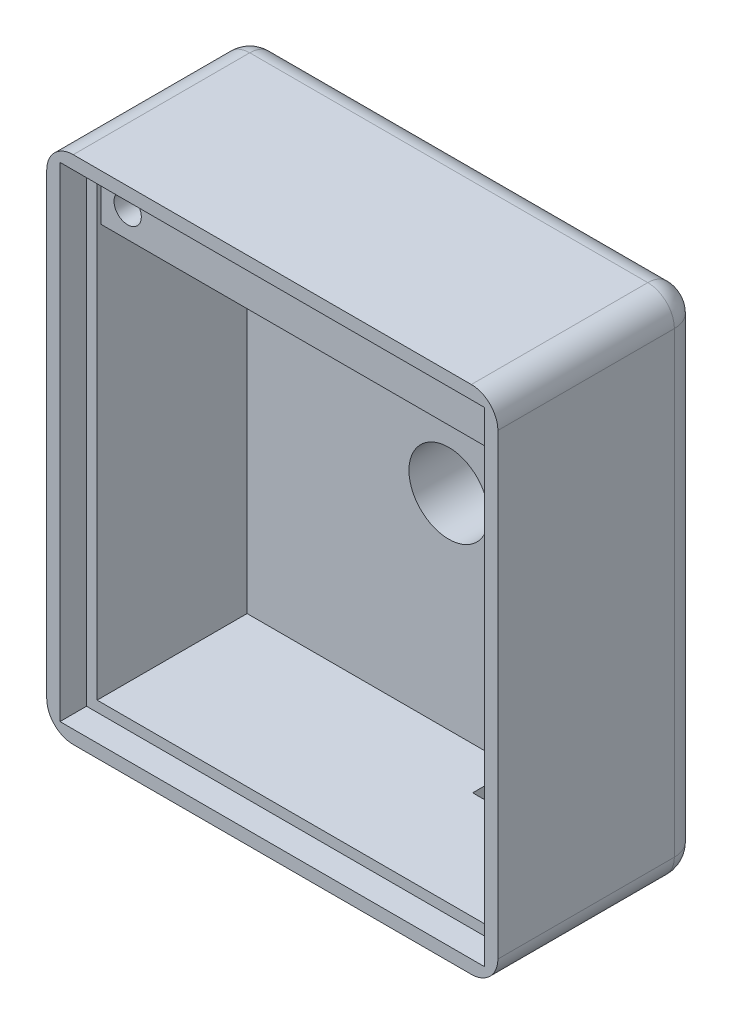
SolidWorks part; units mm, degrees
ref_plane "Front Plane" through (0, 0, 0) normal (0, 0, 1) x (1, 0, 0)
ref_plane "Top Plane" through (0, 0, 0) normal (0, 1, 0) x (1, 0, 0)
ref_plane "Right Plane" through (0, 0, 0) normal (1, 0, 0) x (0, 0, -1)
sketch "Sketch1" plane through (0, 0, 0) normal (0, 0, 1) x (1, 0, 0)
  line L1 (-8.25, 36.25) -> (25.75, 36.25)
  line L2 (-8.25, 36.25) -> (-8.25, -2.25)
  line L3 (-8.25, -2.25) -> (25.75, -2.25)
  line L4 (25.75, 36.25) -> (25.75, -2.25)
  dimension "D1" = 34
  dimension "D2" = 38.5
extrude "Extrude1" add sketch "Sketch1" against normal blind 10 and the other way blind 5.3
sketch "Sketch2" plane through (0, 0, -10) normal (0, 0, -1) x (-1, 0, 0)
  line L1 (-8.75, 36.25) -> (-8.75, -2.25) construction
  line L2 (-25.75, 36.25) -> (8.25, 36.25) construction
  line L3 (8.25, -2.25) -> (-25.75, -2.25) construction
  line L4 (-25.75, 17) -> (8.25, 17) construction
  line L7 (-25.75, -2.25) -> (-25.75, 36.25) construction
  line L8 (8.25, 36.25) -> (8.25, -2.25) construction
  circle A0 centre (-8.75, 17) radius 8
  dimension "D1" = 16
sketch "Sketch5" plane through (0, 0, 5.3) normal (0, 0, 1) x (1, 0, 0)
  line L0 (25.75, -2.25) -> (25.75, 36.25) construction
  line L1 (24.75, -1.25) -> (-7.25, -1.25)
  line L2 (24.75, -1.25) -> (24.75, 35.25)
  line L3 (24.75, 35.25) -> (-7.25, 35.25)
  line L4 (-7.25, -1.25) -> (-7.25, 35.25)
  line L5 (-8.25, -2.25) -> (25.75, -2.25) construction
  line L6 (-8.25, 36.25) -> (-8.25, -2.25) construction
  line L7 (25.75, 36.25) -> (-8.25, 36.25) construction
  dimension "D1" = 1
  dimension "D2" = 1
  dimension "D3" = 1
  dimension "D4" = 1
extrude "Cut-Extrude2" cut sketch "Sketch5" against normal blind 2
sketch "Sketch6" plane through (0, 0, 3.3) normal (0, 0, 1) x (1, 0, 0)
  line L0 (25.75, -2.25) -> (25.75, 36.25) construction
  line L1 (23.95, -0.45) -> (-6.45, -0.45)
  line L2 (23.95, -0.45) -> (23.95, 34.45)
  line L3 (23.95, 34.45) -> (-6.45, 34.45)
  line L4 (-6.45, -0.45) -> (-6.45, 34.45)
  line L5 (-8.25, -2.25) -> (25.75, -2.25) construction
  line L6 (-8.25, 36.25) -> (-8.25, -2.25) construction
  line L7 (25.75, 36.25) -> (-8.25, 36.25) construction
  dimension "D1" = 1.8
  dimension "D2" = 1.8
  dimension "D3" = 1.8
  dimension "D4" = 1.8
extrude "Cut-Extrude3" cut sketch "Sketch6" against normal blind 11.3 and the other way blind 0.2
fillet "Fillet1" radius 2 8 edges at (8.75, 36.25, -10) (-8.25, 17, -10) (25.75, 17, -10) (8.75, -2.25, -10) (25.75, -2.25, -2.35) (25.75, 36.25, -2.35) (-8.25, -2.25, -2.35) (-8.25, 36.25, -2.35)
sketch "Sketch11" plane through (0, 0, -8) normal (0, 0, 1) x (1, 0, 0)
  line L0 (-6.45, 34.45) -> (23.95, 34.45) construction
  line L1 (23.95, 34.45) -> (23.95, 30.45)
  line L2 (23.95, -0.45) -> (23.95, 34.45) construction
  line L3 (-6.45, 34.45) -> (-0.45, 29.95) construction
  line L4 (23.95, 30.45) -> (-6.45, 30.45)
  line L5 (23.95, 34.45) -> (-6.45, 34.45)
  line L6 (-6.45, 30.45) -> (-6.45, 34.45)
  dimension "D1" = 30.4
  dimension "D2" = 4
extrude "Extrude4" add sketch "Sketch11" along normal blind 11
hole_wizard "#1 Clearance Hole1" positions "Sketch13" profile "Sketch12" hole size "#1" standard "Ansi Inch"
sketch "Sketch13" plane through (0, 0, 3.3) normal (0, 0, 1) x (1, 0, 0)
  line L2 (23.75, 36.25) -> (-6.25, 36.25) construction
  line L3 (-8.25, 34.25) -> (-8.25, -0.25) construction
  point P0 (-4.45, 32.45)
  dimension "D1" = 3.8
  dimension "D2" = 3.8
sketch "Sketch12" plane through (-4.45, 32.45, 3.3) normal (1, 0, 0) x (0, -1, 0)
  line L0 (0, 0) -> (0, 8.6181)
  line L1 (0, 8.6181) -> (1.0287, 8)
  line L2 (1.0287, 8) -> (1.0287, 0)
  line L5 (1.0287, 0) -> (0, 0)
  line L10 (0, 8.6181) -> (-1.0287, 8) construction
  line L11 (0, -6.35) -> (0, 107.95) construction
  dimension "Hole Dia." = 2.0574
  dimension "Hole Depth" = 8
  dimension "Drill Angle" = 118
sketch "Sketch17" plane through (0, 0, -10) normal (0, 0, -1) x (-1, 0, 0)
  line L0 (6.45, 30.45) -> (6.45, -0.45) construction
  line L1 (6.45, 15) -> (-23.95, 15) construction
  line L2 (-23.95, -0.45) -> (-23.95, 30.45) construction
  line L3 (-8.75, 30.45) -> (-8.75, -0.45) construction
  line L4 (6.45, 30.45) -> (-23.95, 30.45) construction
  line L7 (-23.95, -0.45) -> (6.45, -0.45) construction
  circle A0 centre (-8.75, 15) radius 3
  dimension "D1" = 6
extrude "Cut-Extrude6" cut sketch "Sketch17" against normal blind 10
sketch "Sketch18" plane through (0, 0, -8) normal (0, 0, 1) x (1, 0, 0)
  line L1 (-6.45, 30.45) -> (-3.45, 30.45)
  line L2 (-6.45, 30.45) -> (-6.45, 27.45)
  line L3 (-6.45, 27.45) -> (-3.45, 27.45)
  line L4 (-3.45, 30.45) -> (-3.45, 27.45)
  dimension "D1" = 3
  dimension "D2" = 3
extrude "Extrude5" add sketch "Sketch18" along normal blind 2.3
sketch "Sketch19" plane through (0, -2.25, 0) normal (0, -1, 0) x (1, 0, 0)
  line L0 (25.75, 5.3) -> (25.75, -8) construction
  line L4 (13.75, -4.8) -> (22.05, -4.8)
  line L5 (13.75, -4.8) -> (13.75, -8)
  line L6 (13.75, -8) -> (22.05, -8)
  line L7 (22.05, -4.8) -> (22.05, -8)
  line L8 (23.75, -10) -> (-6.25, -10) construction
  dimension "D1" = 3.7
  dimension "D2" = 8.3
  dimension "D3" = 3.2
  dimension "D4" = 2
extrude "Cut-Extrude7" cut sketch "Sketch19" against normal blind 3
sketch "Sketch20" plane through (0, 0, -10) normal (0, 0, -1) x (-1, 0, 0)
  circle A1 centre (-8.75, 15) radius 3 construction
  circle A3 centre (-8.75, 15) radius 8.5
  dimension "D1" = 17
extrude "Extrude6" add sketch "Sketch20" along normal blind 6
sketch "Sketch21" plane through (0, 0, -16) normal (0, 0, -1) x (-1, 0, 0)
  circle A3 centre (-8.75, 15) radius 6.6
  dimension "D1" = 13.2
extrude "Cut-Extrude8" cut sketch "Sketch21" against normal blind 6
sketch "Sketch22" plane through (0, 0, -10) normal (0, 0, -1) x (-1, 0, 0)
  circle A3 centre (-8.75, 15) radius 4.45
  dimension "D1" = 8.9
extrude "Extrude7" add sketch "Sketch22" along normal blind 6
sketch "Sketch23" plane through (0, 0, -16) normal (0, 0, -1) x (-1, 0, 0)
  circle A3 centre (-8.75, 15) radius 3
  dimension "D1" = 6
extrude "Cut-Extrude9" cut sketch "Sketch23" against normal blind 6
fillet "Fillet2" radius 1 1 edges at (2.15, 15, -16)
fillet "Fillet3" radius 1 1 edges at (0.25, 15, -16)
fillet "Fillet4" radius 1 1 edges at (5.75, 15, -16)
fillet "Fillet5" radius 1 1 edges at (4.3, 15, -16)
fillet "Fillet6" radius 2 1 edges at (17.25, 15, -10)
fillet "Fillet7" radius 1 3 edges at (22.05, -2.25, -6.4) (13.75, -2.25, -6.4) (17.9, -2.25, -4.8)
